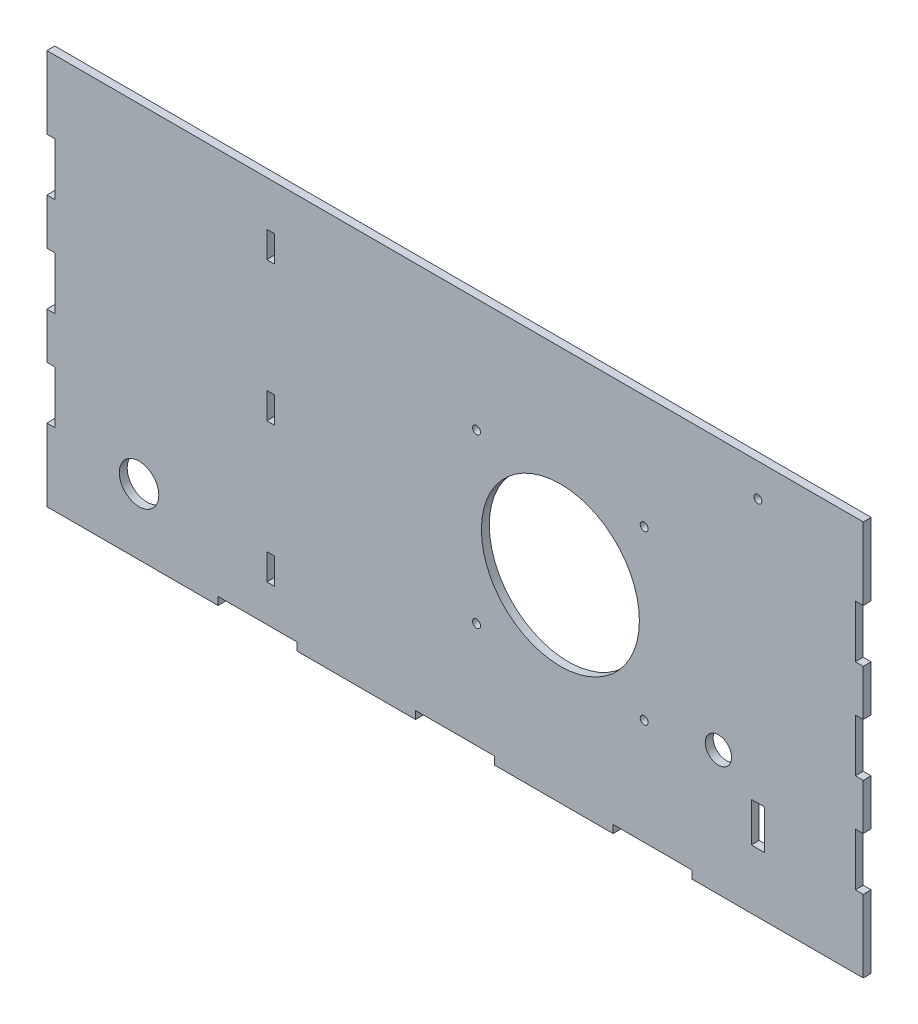
SolidWorks part; units mm, degrees
material "ABS"
ref_plane "Plan de face" through (0, 0, 0) normal (0, 0, 1) x (1, 0, 0)
ref_plane "Plan de dessus" through (0, 0, 0) normal (0, 1, 0) x (1, 0, 0)
ref_plane "Plan de droite" through (0, 0, 0) normal (1, 0, 0) x (0, 0, -1)
sketch "Esquisse1" plane through (0, 0, 0) normal (0, 0, 1) x (1, 0, 0)
  line L1 (155, -75) -> (-155, -75)
  line L2 (155, -75) -> (155, 75)
  line L3 (155, 75) -> (-155, 75)
  line L4 (-155, -75) -> (-155, 75)
  line L5 (155, -75) -> (-155, 75) construction
  line L6 (155, 75) -> (-155, -75) construction
  point P0 (0, 0)
  dimension "D1" = 310
  dimension "D2" = 150
extrude "Boss.-Extru.1" add sketch "Esquisse1" along normal blind 3
sketch "Esquisse2" plane through (0, 0, 0) normal (0, 0, -1) x (-1, 0, 0)
  line L0 (-155, 0) -> (155, 0) construction
  line L1 (-75, 0) -> (-75, -75) construction
  line L2 (75, 0) -> (75, -75) construction
  line L3 (-155, -75) -> (-155, 75) construction
  line L4 (75, 0) -> (75, 75) construction
  line L5 (-60, -78) -> (-90, -78)
  line L126 (155, 75) -> (155, -75) construction
  line L127 (0, -75) -> (0, 0) construction
  line L128 (155, -75) -> (-155, -75) construction
  line L129 (-60, -78) -> (-60, -72)
  line L130 (-60, -72) -> (-90, -72)
  line L131 (-90, -78) -> (-90, -72)
  line L132 (-60, -78) -> (-90, -72) construction
  line L133 (-60, -72) -> (-90, -78) construction
  line L134 (15, -78) -> (-15, -78)
  line L135 (15, -78) -> (15, -72)
  line L136 (15, -72) -> (-15, -72)
  line L137 (-15, -78) -> (-15, -72)
  line L138 (15, -78) -> (-15, -72) construction
  line L139 (15, -72) -> (-15, -78) construction
  line L140 (90, -78) -> (60, -78)
  line L141 (90, -78) -> (90, -72)
  line L142 (90, -72) -> (60, -72)
  line L143 (60, -78) -> (60, -72)
  line L144 (90, -78) -> (60, -72) construction
  line L145 (90, -72) -> (60, -78) construction
  line L146 (-155, 75) -> (155, 75) construction
  line L147 (75, -37.5) -> (155, -37.5) construction
  line L148 (75, 37.5) -> (155, 37.5) construction
  line L149 (75, 37.5) -> (-155, 37.5) construction
  line L150 (158, 27.5) -> (152, 27.5)
  line L151 (158, 27.5) -> (158, 47.5)
  line L152 (158, 47.5) -> (152, 47.5)
  line L153 (152, 27.5) -> (152, 47.5)
  line L154 (158, 27.5) -> (152, 47.5) construction
  line L155 (158, 47.5) -> (152, 27.5) construction
  line L156 (158, -10) -> (152, -10)
  line L157 (158, -10) -> (158, 10)
  line L158 (158, 10) -> (152, 10)
  line L159 (152, -10) -> (152, 10)
  line L160 (158, -10) -> (152, 10) construction
  line L161 (158, 10) -> (152, -10) construction
  line L162 (158, -47.5) -> (152, -47.5)
  line L163 (158, -47.5) -> (158, -27.5)
  line L164 (158, -27.5) -> (152, -27.5)
  line L165 (152, -47.5) -> (152, -27.5)
  line L166 (158, -47.5) -> (152, -27.5) construction
  line L167 (158, -27.5) -> (152, -47.5) construction
  line L168 (75, -37.5) -> (-155, -37.5) construction
  line L170 (-158, 27.5) -> (-152, 27.5)
  line L171 (-158, 27.5) -> (-158, 47.5)
  line L172 (-158, 47.5) -> (-152, 47.5)
  line L173 (-152, 27.5) -> (-152, 47.5)
  line L174 (-158, 27.5) -> (-152, 47.5) construction
  line L175 (-158, 47.5) -> (-152, 27.5) construction
  line L176 (-158, -10) -> (-152, -10)
  line L177 (-158, -10) -> (-158, 10)
  line L178 (-158, 10) -> (-152, 10)
  line L179 (-152, -10) -> (-152, 10)
  line L180 (-158, -10) -> (-152, 10) construction
  line L181 (-158, 10) -> (-152, -10) construction
  line L182 (-158, -47.5) -> (-152, -47.5)
  line L183 (-158, -47.5) -> (-158, -27.5)
  line L184 (-158, -27.5) -> (-152, -27.5)
  line L185 (-152, -47.5) -> (-152, -27.5)
  line L186 (-158, -47.5) -> (-152, -27.5) construction
  line L187 (-158, -27.5) -> (-152, -47.5) construction
  dimension "D1" = 75
  dimension "D2" = 75
  dimension "D3" = 30
  dimension "D4" = 6
  dimension "D5" = 20
  dimension "D6" = 6
  dimension "D7" = 6
  dimension "D8" = 20
sketch "Esquisse3" plane through (0, 0, 0) normal (0, 0, -1) x (-1, 0, 0)
  line L0 (0, 0) -> (-40, 0) construction
  circle A0 centre (-40, 0) radius 30
  dimension "D1" = 60
  dimension "D2" = 40
extrude "Enlèv. mat.-Extru.2" cut sketch "Esquisse3" against normal blind 10
sketch "Esquisse4" plane through (0, 0, 0) normal (0, 0, -1) x (-1, 0, 0)
  line L1 (-5, -35) -> (-75, -35) construction
  line L2 (-5, -35) -> (-5, 35) construction
  line L3 (-5, 35) -> (-75, 35) construction
  line L4 (-75, -35) -> (-75, 35) construction
  line L5 (-5, -35) -> (-75, 35) construction
  line L6 (-5, 35) -> (-75, -35) construction
  line L7 (-56, 33) -> (-60, 33)
  line L8 (-56, 33) -> (-56, 37)
  line L9 (-56, 37) -> (-60, 37)
  line L10 (-60, 33) -> (-60, 37)
  line L11 (-56, 33) -> (-60, 37) construction
  line L12 (-56, 37) -> (-60, 33) construction
  line L13 (-20, 33) -> (-24, 33)
  line L14 (-20, 33) -> (-20, 37)
  line L15 (-20, 37) -> (-24, 37)
  line L16 (-24, 33) -> (-24, 37)
  line L17 (-20, 33) -> (-24, 37) construction
  line L18 (-20, 37) -> (-24, 33) construction
  line L19 (-3, 16) -> (-7, 16)
  line L20 (-3, 16) -> (-3, 20)
  line L21 (-3, 20) -> (-7, 20)
  line L22 (-7, 16) -> (-7, 20)
  line L23 (-3, 16) -> (-7, 20) construction
  line L24 (-3, 20) -> (-7, 16) construction
  line L25 (-3, -20) -> (-7, -20)
  line L26 (-3, -20) -> (-3, -16)
  line L27 (-3, -16) -> (-7, -16)
  line L28 (-7, -20) -> (-7, -16)
  line L29 (-3, -20) -> (-7, -16) construction
  line L30 (-3, -16) -> (-7, -20) construction
  line L31 (-24, -37) -> (-20, -37)
  line L32 (-24, -37) -> (-24, -33)
  line L33 (-24, -33) -> (-20, -33)
  line L34 (-20, -37) -> (-20, -33)
  line L35 (-24, -37) -> (-20, -33) construction
  line L36 (-24, -33) -> (-20, -37) construction
  line L37 (-56, -37) -> (-60, -37)
  line L38 (-56, -37) -> (-56, -33)
  line L39 (-56, -33) -> (-60, -33)
  line L40 (-60, -37) -> (-60, -33)
  line L41 (-56, -37) -> (-60, -33) construction
  line L42 (-56, -33) -> (-60, -37) construction
  line L43 (-73, 16) -> (-77, 16)
  line L44 (-73, 16) -> (-73, 20)
  line L45 (-73, 20) -> (-77, 20)
  line L46 (-77, 16) -> (-77, 20)
  line L47 (-73, 16) -> (-77, 20) construction
  line L48 (-73, 20) -> (-77, 16) construction
  line L49 (-73, -20) -> (-77, -20)
  line L50 (-73, -20) -> (-73, -16)
  line L51 (-73, -16) -> (-77, -16)
  line L52 (-77, -20) -> (-77, -16)
  line L53 (-73, -20) -> (-77, -16) construction
  line L54 (-73, -16) -> (-77, -20) construction
  point P0 (-40, 0)
  point P6 (-58, 35)
  point P11 (-22, 35)
  point P16 (-5, 18)
  point P21 (-5, -18)
  point P26 (-22, -35)
  point P31 (-58, -35)
  point P36 (-75, 18)
  point P41 (-75, -18)
  dimension "D1" = 70
  dimension "D2" = 4
  dimension "D3" = 15
  dimension "D4" = 15
  dimension "D5" = 15
  dimension "D6" = 15
  dimension "D7" = 15
  dimension "D8" = 15
  dimension "D9" = 15
  dimension "D10" = 15
extrude "Enlèv. mat.-Extru.3" [suppressed] cut sketch "Esquisse4" against normal through all
sketch "Esquisse5" plane through (0, 0, 0) normal (0, 0, -1) x (-1, 0, 0)
  line L0 (-71.8198, 31.8198) -> (-8.1802, -31.8198) construction
  line L1 (-71.8198, -31.8198) -> (-8.1802, 31.8198) construction
  line L2 (-71.8198, 31.8198) -> (-8.1802, 31.8198) construction
  circle A0 centre (-40, 0) radius 45 construction
  circle A1 centre (-71.8198, 31.8198) radius 1.5
  circle A2 centre (-71.8198, -31.8198) radius 1.5
  circle A3 centre (-8.1802, -31.8198) radius 1.5
  circle A4 centre (-8.1802, 31.8198) radius 1.5
  circle A5 centre (-40, 0) radius 30 construction
  circle A6 centre (-40, 0) radius 30 construction
  dimension "D2" = 3
  dimension "D1" = 90
extrude "Enlèv. mat.-Extru.4" cut sketch "Esquisse5" against normal blind 10
sketch "Esquisse6" plane through (0, 0, 0) normal (0, 0, -1) x (-1, 0, 0)
  circle A0 centre (120, -50) radius 7.5
  dimension "D1" = 15
  dimension "D2" = 120
  dimension "D3" = 50
extrude "Enlèv. mat.-Extru.5" cut sketch "Esquisse6" against normal blind 10
sketch "Esquisse7" plane through (0, 0, 0) normal (0, 0, -1) x (-1, 0, 0)
  line L0 (70, 65) -> (70, -65) construction
  line L1 (0, 0) -> (70, 0) construction
  line L2 (70, -53) -> (70, 53) construction
  line L4 (71.5, 58) -> (68.5, 58)
  line L5 (71.5, 58) -> (71.5, 48)
  line L6 (71.5, 48) -> (68.5, 48)
  line L7 (68.5, 58) -> (68.5, 48)
  line L8 (71.5, 58) -> (68.5, 48) construction
  line L9 (71.5, 48) -> (68.5, 58) construction
  line L10 (71.5, 5) -> (68.5, 5)
  line L11 (71.5, 5) -> (71.5, -5)
  line L12 (71.5, -5) -> (68.5, -5)
  line L13 (68.5, 5) -> (68.5, -5)
  line L14 (71.5, 5) -> (68.5, -5) construction
  line L15 (71.5, -5) -> (68.5, 5) construction
  line L16 (71.5, -58) -> (68.5, -58)
  line L17 (71.5, -58) -> (71.5, -48)
  line L18 (71.5, -48) -> (68.5, -48)
  line L19 (68.5, -58) -> (68.5, -48)
  line L20 (71.5, -58) -> (68.5, -48) construction
  line L21 (71.5, -48) -> (68.5, -58) construction
  point P7 (70, 0)
  dimension "D1" = 70
  dimension "D2" = 130
  dimension "D3" = 106
  dimension "D4" = 10
  dimension "D5" = 3
  dimension "D6" = 3
  dimension "D7" = 3
  dimension "D8" = 10
  dimension "D9" = 10
extrude "Enlèv. mat.-Extru.6" cut sketch "Esquisse7" against normal blind 10
extrude "Enlèv. mat.-Extru.7" cut sketch "Esquisse2" against normal blind 10
sketch "Esquisse8" plane through (0, 0, 0) normal (0, 0, -1) x (-1, 0, 0)
  line L0 (-155, -75) -> (-155, -47.5) construction
  line L1 (-112.5, -52.5) -> (-117.5, -52.5)
  line L2 (-112.5, -52.5) -> (-112.5, -37.5)
  line L3 (-112.5, -37.5) -> (-117.5, -37.5)
  line L4 (-117.5, -52.5) -> (-117.5, -37.5)
  line L5 (-112.5, -52.5) -> (-117.5, -37.5) construction
  line L6 (-112.5, -37.5) -> (-117.5, -52.5) construction
  line L7 (-90, -75) -> (-155, -75) construction
  point P0 (-115, -45)
  dimension "D1" = 40
  dimension "D2" = 30
  dimension "D3" = 5
  dimension "D4" = 15
extrude "Enlèv. mat.-Extru.8" cut sketch "Esquisse8" against normal blind 10
sketch "Esquisse9" plane through (0, 0, 0) normal (0, 0, -1) x (-1, 0, 0)
  line L0 (-127.5, -37.5) -> (-127.5, -52.5) construction
  line L1 (-117.5, -37.5) -> (-117.5, -52.5) construction
  text T0 "  RGB"
  dimension "D1" = 10
extrude "Enlèv. mat.-Extru.9" cut sketch "Esquisse9" against normal blind 1
sketch "Esquisse10" plane through (0, 0, 0) normal (0, 0, -1) x (-1, 0, 0)
  line L0 (-71.8198, 38.8198) -> (-8.1802, 38.8198) construction
  line L1 (-8.1802, 31.8198) -> (-8.1802, -31.8198) construction
  line L2 (-71.8198, 31.8198) -> (-71.8198, -31.8198) construction
  text T0 "     FEEDING MECHANISM"
  dimension "D1" = 7
extrude "Enlèv. mat.-Extru.10" cut sketch "Esquisse10" against normal blind 1
sketch "Esquisse11" plane through (0, 0, 0) normal (0, 0, -1) x (-1, 0, 0)
  circle A0 centre (120, -50) radius 12.5 construction
  text T0 "TEMPERATURE "
  dimension "D1" = 25
extrude "Enlèv. mat.-Extru.11" cut sketch "Esquisse11" against normal blind 1
sketch "Esquisse12" plane through (0, 0, 0) normal (0, 0, -1) x (-1, 0, 0)
  line L0 (-115, -37.5) -> (-115, 75) construction
  line L1 (-112.5, -37.5) -> (-117.5, -37.5) construction
  line L2 (-155, 75) -> (155, 75) construction
  circle A0 centre (-115, 62.5) radius 1.5
  circle A1 centre (-100, -27.5) radius 5
  dimension "D1" = 3
  dimension "D5" = 10
  dimension "D2" = 100
  dimension "D3" = 15
  dimension "D4" = 10
extrude "Enlèv. mat.-Extru.12" cut sketch "Esquisse12" against normal blind 10
sketch "Esquisse13" plane through (0, 0, 0) normal (0, 0, -1) x (-1, 0, 0)
  line L0 (-110.2552, -17.5) -> (-90.2552, -17.5) construction
  circle A0 centre (-100, -27.5) radius 5 construction
  text T0 "PUMP\r\n"
  dimension "D1" = 10
  dimension "D2" = 20
extrude "Enlèv. mat.-Extru.13" cut sketch "Esquisse13" against normal blind 1
equation "\"é\"=10"
